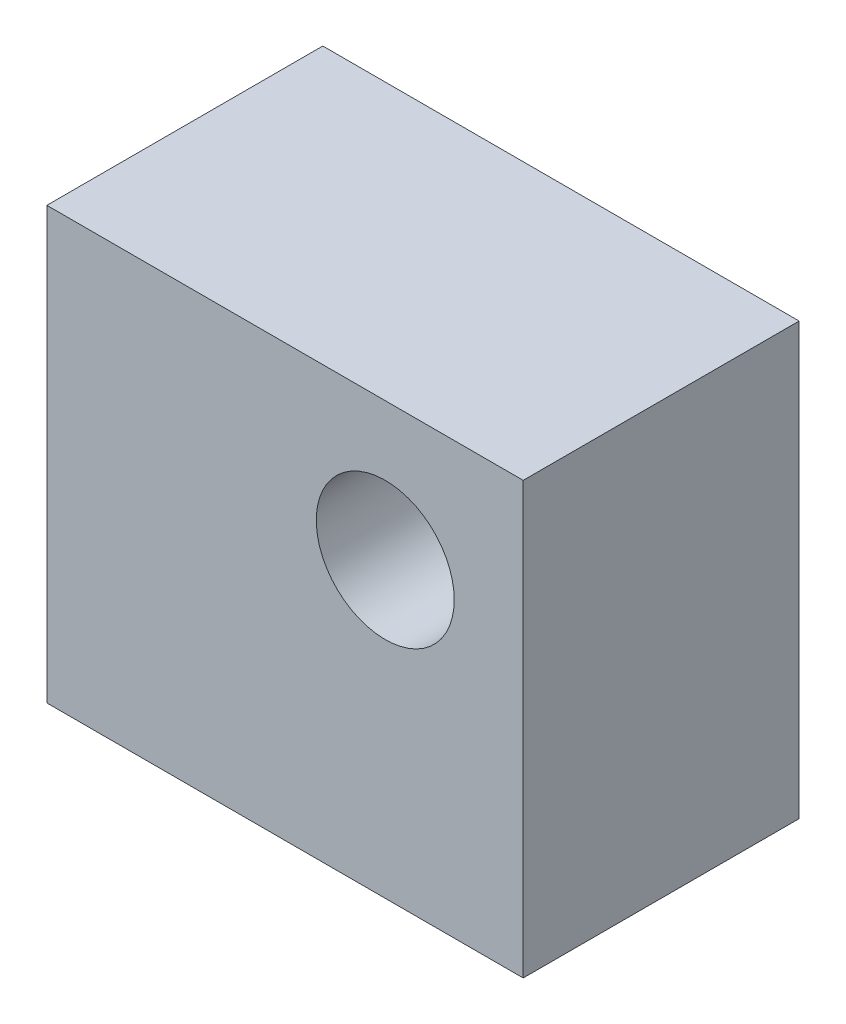
SolidWorks part; units mm, degrees
material "1060 Alloy"
ref_plane "Front" through (0, 0, 0) normal (0, 0, 1) x (1, 0, 0)
ref_plane "Top" through (0, 0, 0) normal (0, 1, 0) x (1, 0, 0)
ref_plane "Right" through (0, 0, 0) normal (1, 0, 0) x (0, 0, -1)
sketch "Sketch3" plane through (0, 0, 0) normal (0, 0, 1) x (1, 0, 0)
  line L0 (-0.127, -6.35) -> (30.1755, -6.35)
  line L1 (0, 0) -> (21.9242, 0)
  line L2 (0, 0) -> (0, -19.8376)
  line L3 (0, -19.8376) -> (21.9242, -19.8376)
  line L4 (21.9242, 0) -> (21.9242, -19.8376)
  line L5 (15.5742, -19.8376) -> (15.5742, 0) construction
  line L6 (15.5742, -6.35) -> (8.0621, -19.3614) construction
  line L15 (12.5496, -11.5887) -> (15.5742, -13.335) construction
  circle A0 centre (15.5742, -6.35) radius 6.0492 construction
  point P14 (0, -6.35)
  point P17 (9.525, -6.35)
  point P20 (7.7871, -19.8376)
  dimension "D2" = 6.35
  dimension "D6" = 3.4925
  dimension "D3" = 60
  dimension "D1" = 9.525
  dimension "D4" = 9.525
  dimension "D5" = 6.35
extrude "Boss-Extrude1" add sketch "Sketch3" along normal mid plane 12.7
sketch "Sketch4" plane through (0, 0, 0) normal (-1, 0, 0) x (0, 0, 1)
  circle A0 centre (0, -6.35) radius 3.175
  dimension "D1" = 6.35
extrude "Cut-Extrude1" cut sketch "Sketch4" against normal blind 9.525
ref_plane "Plane1" through (7.7871, -19.8376, 0) normal (-0.5, -0.866, 0) x (-0.866, 0.5, 0)
ref_plane "Mirror Plane" through (15.5742, 0, 0) normal (-1, 0, 0) x (0, 0, 1)
sketch "Sketch5" plane through (7.7871, -19.8376, 0) normal (-0.5, -0.866, 0) x (-0.866, 0.5, 0)
  circle A0 centre (0, 0) radius 3.175
  dimension "D1" = 6.35
extrude "Cut-Extrude5" cut sketch "Sketch5" against normal blind 9.525 and the other way up to next
sketch "Sketch6" plane through (0, 0, 6.35) normal (0, 0, -1) x (-1, 0, 0)
  circle A0 centre (-15.5742, -6.35) radius 3.175
  dimension "D1" = 6.35
extrude "Cut-Extrude6" cut sketch "Sketch6" along normal blind 9.525
equation "\"truss_member_od\"= .25in"
equation "\"truss_member_id\"= 0in"
equation "\"truss_member_L1\"= 2.125in"
equation "\"connector_hole_depth\"= .375in"
equation "\"D1@Boss-Extrude1\"=\"truss_member_od\"*2"
equation "\"D6@Sketch3\"=\"truss_member_od\"/2*1.1"
equation "\"D1@Sketch4\"=\"truss_member_od\""
equation "\"D1@Cut-Extrude1\"=\"connector_hole_depth\""
equation "\"D1@Sketch3\"=\"connector_hole_depth\""
equation "\"D4@Sketch3\"=\"connector_hole_depth\""
equation "\"D1@Sketch5\"=\"truss_member_od\""
equation "\"D1@Cut-Extrude5\"=\"connector_hole_depth\""
equation "\"D1@Cut-Extrude6\"=\"connector_hole_depth\""
equation "\"D1@Sketch6\"=\"truss_member_od\""
equation "\"D5@Sketch3\"=\"truss_member_od\""
